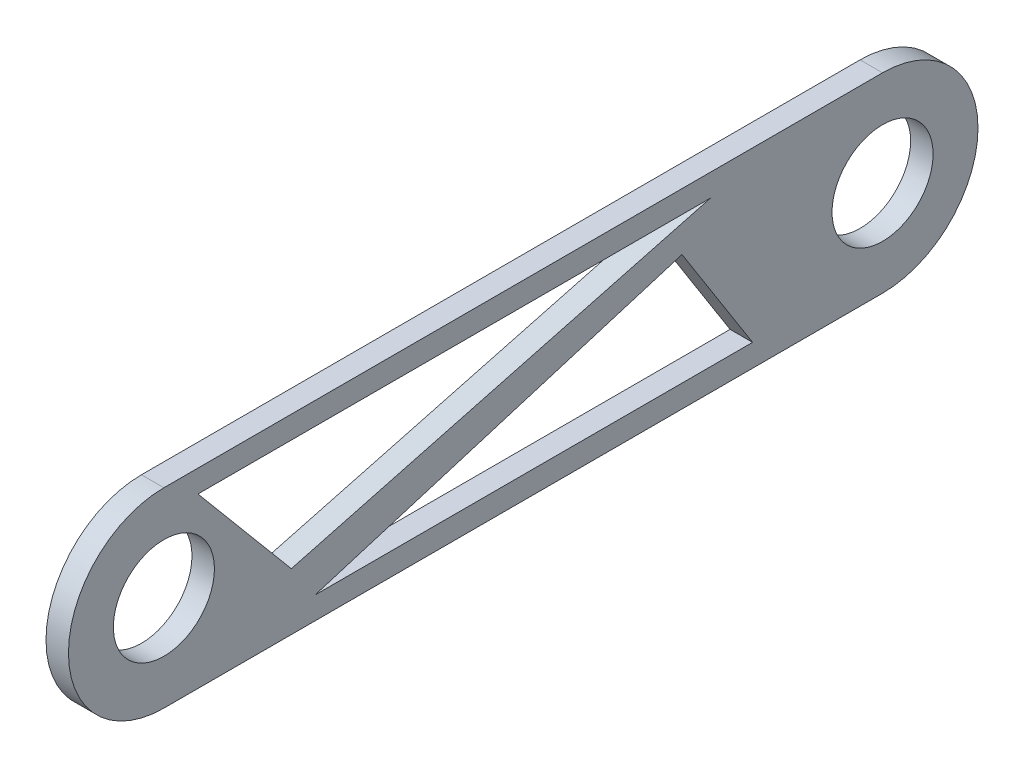
SolidWorks part; units mm, degrees
material "PC High Viscosity"
ref_plane "Front Plane" through (0, 0, 0) normal (0, 0, 1) x (1, 0, 0)
ref_plane "Top Plane" through (0, 0, 0) normal (0, 1, 0) x (1, 0, 0)
ref_plane "Right Plane" through (0, 0, 0) normal (1, 0, 0) x (0, 0, -1)
sketch "Sketch1" plane through (0, 0, 0) normal (1, 0, 0) x (0, 0, -1)
  line L0 (0, 26.9875) -> (203.2, 26.9875)
  line L1 (0, -26.9875) -> (203.2, -26.9875)
  line L2 (203.2, -26.9875) -> (203.2, 26.9875) construction
  line L3 (0, -26.9875) -> (203.2, 26.9875) construction
  line L4 (9.6255, 20.6375) -> (36.0341, -10.8457)
  line L5 (36.0341, -10.8457) -> (154.5592, 20.6375)
  line L6 (154.5592, 20.6375) -> (9.6255, 20.6375)
  line L7 (0, 26.9875) -> (203.2, -26.9875) construction
  line L8 (101.6, 0) -> (101.6, -26.9875) construction
  line L12 (101.6, 0) -> (-26.9875, 0) construction
  line L13 (166.4488, -20.6375) -> (146.4874, 10.8457)
  line L14 (42.7779, -20.6375) -> (166.4488, -20.6375)
  line L15 (146.4874, 10.8457) -> (42.7779, -20.6375)
  circle A0 centre (0, 0) radius 14.2875
  arc A1 (0, 26.9875) -> (0, -26.9875) centre (0, 0) ccw
  arc A2 (203.2, -26.9875) -> (203.2, 26.9875) centre (203.2, 0) ccw
  circle A3 centre (203.2, 0) radius 14.2875
  dimension "D1" = 28.575
  dimension "D2" = 12.7
  dimension "D5" = 28.575
  dimension "D3" = 203.2
  dimension "D4" = 203.2
  dimension "D6" = 6.35
  dimension "D7" = 6.35
  dimension "D8" = 20.6375
  dimension "D9" = 10.8457
extrude "Boss-Extrude1" add sketch "Sketch1" along normal blind 6.35 contours L1 A2 L0 A1 A3 L6 L5 L4 L15 L13 L14 A0 region at (0, -0.4384, -107.6032)
